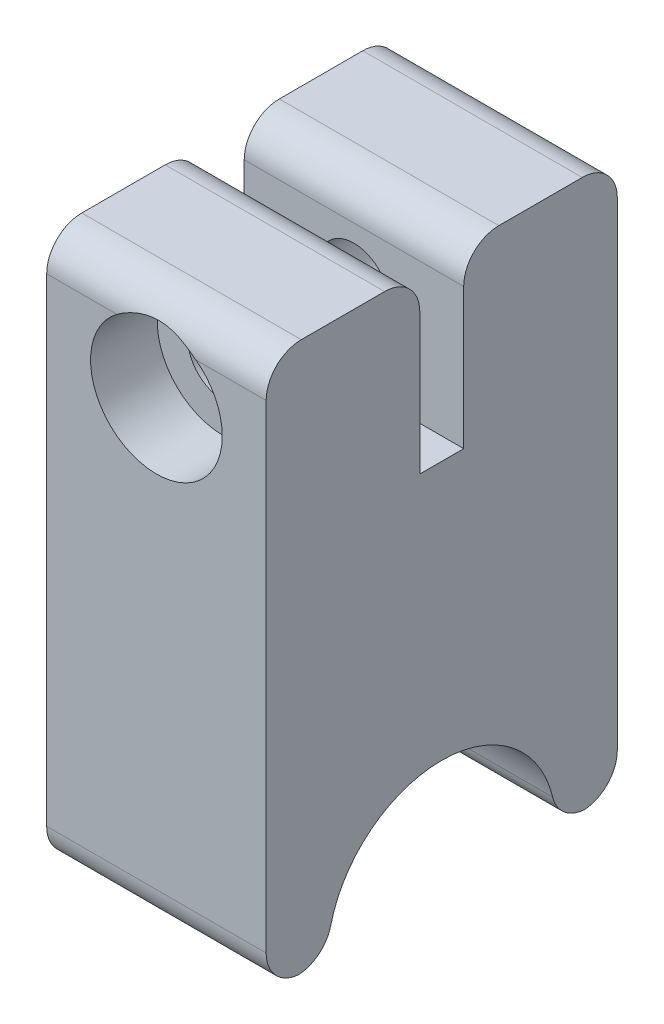
SolidWorks part; units mm, degrees
material "Delrin 2700 NC010, Low Viscosity Acetal Copolymer (SS)"
ref_plane "Front Plane" through (0, 0, 0) normal (0, 0, 1) x (1, 0, 0)
ref_plane "Top Plane" through (0, 0, 0) normal (0, 1, 0) x (1, 0, 0)
ref_plane "Right Plane" through (0, 0, 0) normal (1, 0, 0) x (0, 0, -1)
sketch "Sketch1" plane through (0, 0, 0) normal (0, 0, 1) x (1, 0, 0)
  line L1 (-7.9375, -19.8438) -> (7.9375, -19.8438)
  line L2 (-7.9375, -19.8438) -> (-7.9375, 19.8438)
  line L3 (-7.9375, 19.8438) -> (7.9375, 19.8438)
  line L4 (7.9375, -19.8438) -> (7.9375, 19.8438)
  line L5 (-7.9375, -19.8438) -> (7.9375, 19.8438) construction
  line L6 (-7.9375, 19.8438) -> (7.9375, -19.8438) construction
  point P0 (0, 0)
  dimension "D1" = 15.875
  dimension "D2" = 39.6875
extrude "Boss-Extrude1" add sketch "Sketch1" along normal mid plane 25.4
sketch "Sketch2" plane through (7.9375, 0, 0) normal (1, 0, 0) x (0, 0, -1)
  line L0 (-12.7, 19.8438) -> (12.7, 19.8438) construction
  line L1 (-1.5875, 19.8438) -> (1.5875, 19.8438)
  line L2 (-1.5875, 19.8438) -> (-1.5875, 7.1438)
  line L3 (-1.5875, 7.1438) -> (1.5875, 7.1438)
  line L4 (1.5875, 19.8438) -> (1.5875, 7.1438)
  line L5 (-12.7, 19.8438) -> (-1.5875, 19.8438) construction
  line L6 (1.5875, 19.8438) -> (12.7, 19.8438) construction
  line L7 (-12.7, -19.8438) -> (12.7, -19.8438) construction
  circle A0 centre (0, -19.8438) radius 8.255
  dimension "D3" = 16.51
  dimension "D1" = 3.175
  dimension "D2" = 12.7
extrude "Cut-Extrude1" cut sketch "Sketch2" against normal through all
hole_wizard "CBORE for #10 Socket Head Cap Screw1" positions "Sketch3" profile "Sketch4" counterbore size "#10" standard "ANSI Inch" end condition through all
sketch "Sketch3" plane through (0, 0, 12.7) normal (0, 0, 1) x (1, 0, 0)
  line L0 (7.9375, 19.8438) -> (-7.9375, 19.8438) construction
  point P0 (0, 13.4938)
  dimension "D1" = 6.35
sketch "Sketch4" plane through (0, 13.4938, 12.7) normal (1, 0, 0) x (0, -1, 0)
  line L0 (0, 0) -> (0, 25.4)
  line L1 (0, 25.4) -> (2.5527, 25.4)
  line L3 (2.5527, 25.4) -> (2.5527, 4.826)
  line L4 (2.5527, 4.826) -> (4.7625, 4.826)
  line L5 (4.7625, 4.826) -> (4.7625, 0)
  line L7 (4.7625, 0) -> (0, 0)
  line L11 (0, -6.35) -> (0, 107.95) construction
  dimension "Thru Hole Dia." = 5.1054
  dimension "Thru Hole Depth" = 25.4
  dimension "C'Bore Dia." = 9.525
  dimension "C'Bore Depth" = 4.826
fillet "Fillet2" radius 2.54 8 edges at (0, -19.8438, 8.255) (0, -19.8438, -8.255) (0, 19.8438, 12.7) (0, -19.8438, 12.7) (0, 19.8438, -12.7) (0, 19.8438, -1.5875) (0, 19.8438, 1.5875) (0, -19.8438, -12.7)
sketch "Sketch5" plane through (0, 0, -12.7) normal (0, 0, -1) x (-1, 0, 0)
  line L1 (5.6459, 13.4937) -> (2.823, 18.3832)
  line L2 (2.823, 18.3832) -> (-2.823, 18.3832)
  line L3 (-2.823, 18.3832) -> (-5.6459, 13.4937)
  line L4 (-5.6459, 13.4937) -> (-2.823, 8.6042)
  line L5 (-2.823, 8.6042) -> (2.823, 8.6042)
  line L6 (2.823, 8.6042) -> (5.6459, 13.4937)
  circle A0 centre (0, 13.4938) radius 4.8895 construction
  dimension "D1" = 9.779
extrude "Cut-Extrude2" cut sketch "Sketch5" against normal blind 6.2071
